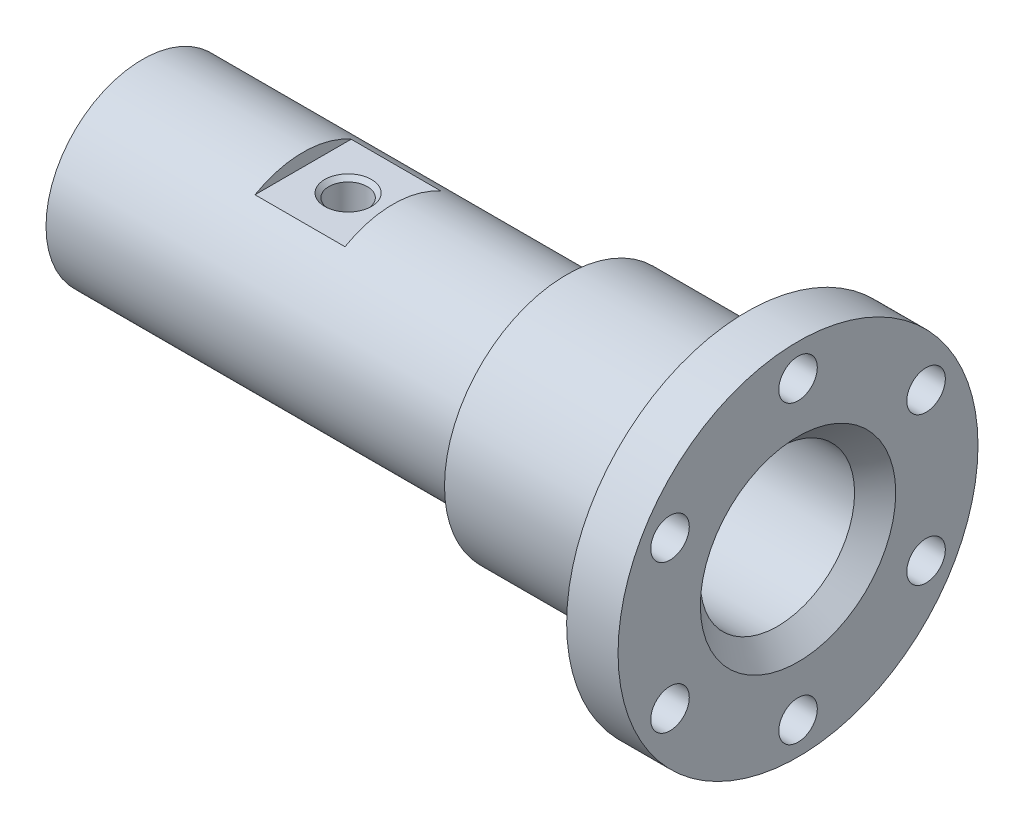
SolidWorks part; units mm, degrees
ref_plane "Front Plane" through (0, 0, 0) normal (0, 0, 1) x (1, 0, 0)
ref_plane "Top Plane" through (0, 0, 0) normal (0, 1, 0) x (1, 0, 0)
ref_plane "Right Plane" through (0, 0, 0) normal (1, 0, 0) x (0, 0, -1)
sketch "Sketch1" plane through (0, 0, 0) normal (0, 0, 1) x (1, 0, 0)
  line L0 (-977.7473, 0) -> (47909.62, 0) construction
  line L1 (103.4783, -30) -> (103.4783, -70)
  line L2 (103.4783, -70) -> (83.4783, -70)
  line L3 (103.4783, -30) -> (43.4783, -30)
  line L4 (83.4783, -70) -> (83.4783, -47.5)
  line L5 (83.4783, -47.5) -> (13.4783, -47.5)
  line L6 (43.4783, -30) -> (43.4783, -22.5)
  line L7 (43.4783, -22.5) -> (-1.5217, -22.5)
  line L8 (-1.5217, -22.5) -> (-1.5217, -27.5)
  line L9 (-1.5217, -27.5) -> (-16.5217, -27.5)
  line L10 (-16.5217, -27.5) -> (-16.5217, -17.5)
  line L11 (-16.5217, -17.5) -> (-106.5217, -17.5)
  line L12 (13.4783, -47.5) -> (13.4783, -37.5)
  line L13 (13.4783, -37.5) -> (-151.5217, -37.5)
  line L14 (-151.5217, -37.5) -> (-151.5217, -22.5)
  line L15 (-151.5217, -22.5) -> (-125.0217, -22.5)
  line L17 (-119.0217, -27.5) -> (-106.5217, -27.5)
  line L18 (-106.5217, -27.5) -> (-106.5217, -17.5)
  line L19 (-119.0217, -27.5) -> (-125.0217, -22.5)
  line L20 (-1165.0429, -24) -> (48834.9571, -24) construction
  point P19 (0, 0)
  dimension "D3" = 18.5
  dimension "D4" = 20
  dimension "D5" = 140
  dimension "D6" = 60
  dimension "D7" = 90
  dimension "D8" = 15
  dimension "D9" = 45
  dimension "D10" = 55
  dimension "D11" = 255
  dimension "D12" = 55
  dimension "D13" = 35
  dimension "D14" = 45
  dimension "D15" = 12.5
  dimension "D16" = 24
  dimension "D17" = 75
  dimension "D18" = 60
  dimension "D19" = 120
  dimension "D20" = 45
  dimension "D21" = 95
revolve "Revolve1" add sketch "Sketch1" angle 360 about L0
fillet "Fillet2" radius 2.5 2 edges at (-106.5217, 0, 27.5) (-119.0217, 0, 27.5)
fillet "Chamfer3" radius 2 1 edges at (-151.5217, 0, 22.5) type face fillet profile chamfer first side face at (-151.5217, 0, 22.5) second side face at (-151.5217, 0, 37.5)
fillet "Chamfer4" radius 8 1 edges at (103.4783, 0, 30) type face fillet profile chamfer first side face at (43.4783, 0, 30) second side face at (103.4783, 0, 30)
sketch "Sketch3" plane through (103.4783, 0, 0) normal (1, 0, 0) x (0, 0, -1)
  circle A0 centre (0, 57.5) radius 7.5
  circle A1 centre (49.7965, 28.75) radius 7.5
  circle A2 centre (49.7965, -28.75) radius 7.5
  circle A3 centre (0, -57.5) radius 7.5
  circle A4 centre (-49.7965, -28.75) radius 7.5
  circle A5 centre (-49.7965, 28.75) radius 7.5
  dimension "D1" = 57.5
  dimension "D2" = 15
  dimension "D3" = 6
extrude "Cut-Extrude1" cut sketch "Sketch3" against normal through all
sketch "Sketch4" plane through (0, 0, 0) normal (0, 0, 1) x (1, 0, 0)
  line L0 (13.4783, 37.5) -> (-151.5217, 37.5) construction
  line L1 (-89.0217, 37.5) -> (-54.0217, 37.5)
  line L2 (-89.0217, 37.5) -> (-89.0217, 32.5)
  line L3 (-89.0217, 32.5) -> (-54.0217, 32.5)
  line L4 (-54.0217, 37.5) -> (-54.0217, 32.5)
  line L5 (-89.0217, 37.5) -> (-54.0217, 32.5) construction
  line L6 (-54.0217, 37.5) -> (-89.0217, 32.5) construction
  line L7 (-151.5217, -37.5) -> (13.4783, -37.5) construction
  point P6 (-71.5217, 35)
  dimension "D1" = 80
  dimension "D2" = 35
  dimension "D3" = 70
extrude "Cut-Extrude2" cut sketch "Sketch4" against normal through all both and the other way through all
sketch "Sketch5" plane through (0, 0, 0) normal (0, 0, 1) x (1, 0, 0)
  line L1 (13.4783, -47.5) -> (43.4783, -47.5)
  line L2 (13.4783, -47.5) -> (13.4783, -41.5)
  line L3 (13.4783, -41.5) -> (43.4783, -41.5)
  line L4 (43.4783, -47.5) -> (43.4783, -41.5)
  dimension "D1" = 30
  dimension "D2" = 6
extrude "Cut-Extrude3" cut sketch "Sketch5" against normal through all both and the other way through all
sketch "Sketch6" plane through (0, 32.5, 0) normal (0, 1, 0) x (1, 0, 0)
  line L0 (-89.0217, 18.7083) -> (-54.0217, -18.7083) construction
  line L1 (-54.0217, -18.7083) -> (-54.0217, 18.7083) construction
  line L2 (-54.0217, 18.7083) -> (-89.0217, -18.7083) construction
  circle A0 centre (-71.5217, 0) radius 7.5
  point P6 (-71.5217, 0)
  dimension "D1" = 15
extrude "Cut-Extrude4" cut sketch "Sketch6" against normal blind 28
fillet "Chamfer5" radius 1.6 1 edges at (-71.5217, 32.5, 7.5) type face fillet profile chamfer first side face at (-70.5008, 15.8443, -7.4302) second side face at (-71.5217, 32.5, 7.5)
sketch "Sketch7" plane through (0, -41.5, 0) normal (0, -1, 0) x (1, 0, 0)
  line L0 (13.4783, 23.1084) -> (43.4783, -23.1084) construction
  line L1 (43.4783, -23.1084) -> (43.4783, 23.1084) construction
  line L2 (43.4783, 23.1084) -> (13.4783, -23.1084) construction
  circle A0 centre (28.4783, 0) radius 9
  dimension "D1" = 18
extrude "Cut-Extrude5" cut sketch "Sketch7" against normal blind 33
chamfer "Chamfer6" distance 1.6 angle 45 1 edges at (28.4783, -41.5, -9)
sketch "Sketch8" plane through (0, 0, 0) normal (0, 0, 1) x (1, 0, 0)
  line L0 (13.4783, -41.5) -> (43.4783, -47.5) construction
  line L1 (43.4783, -47.5) -> (43.4783, -41.5) construction
  line L2 (43.4783, -41.5) -> (13.4783, -41.5) construction
  line L3 (43.4783, -41.5) -> (13.4783, -47.5) construction
  line L4 (28.4783, -1044.5) -> (28.4783, 48955.5) construction
  line L5 (13.4783, -41.5) -> (13.4783, -47.5) construction
  line L6 (13.4783, -47.5) -> (43.4783, -47.5) construction
  line L7 (-1000, 0) -> (49000, 0) construction
  circle A0 centre (28.4783, 0) radius 6
  point P4 (28.4783, 0)
  point P14 (28.4783, -44.5)
  dimension "D1" = 12
extrude "Cut-Extrude6" cut sketch "Sketch8" against normal blind 60
